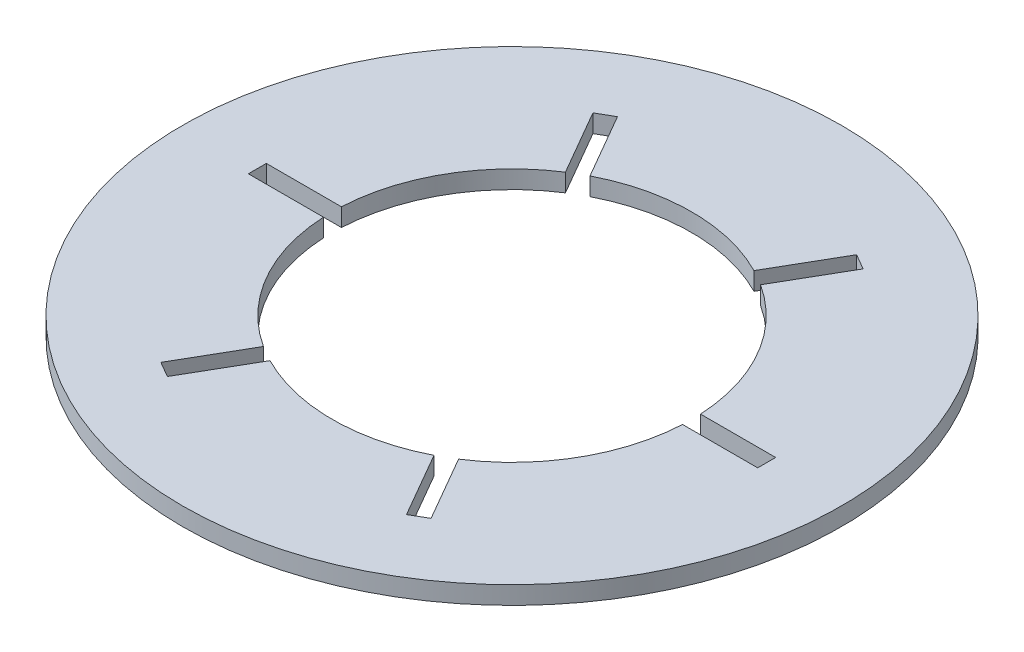
SolidWorks part; units mm, degrees
ref_plane "Front Plane" through (0, 0, 0) normal (0, 0, 1) x (1, 0, 0)
ref_plane "Top Plane" through (0, 0, 0) normal (0, 1, 0) x (1, 0, 0)
ref_plane "Right Plane" through (0, 0, 0) normal (1, 0, 0) x (0, 0, -1)
sketch "Sketch1" plane through (0, 0, 0) normal (0, 1, 0) x (1, 0, 0)
  circle A0 centre (0, 0) radius 55
  dimension "D1" = 110
extrude "Boss-Extrude1" add sketch "Sketch1" along normal blind 3
sketch "Sketch2" plane through (0, 3, 0) normal (0, 1, 0) x (1, 0, 0)
  circle A0 centre (0, 0) radius 30
  dimension "D1" = 60
extrude "Cut-Extrude1" cut sketch "Sketch2" against normal blind 3
sketch "Sketch3" plane through (0, 3, 0) normal (0, 1, 0) x (1, 0, 0)
  line L0 (73.8169, 0) -> (-73.8169, 0) construction
  line L1 (0, -87.0918) -> (0, 87.0918) construction
  line L3 (-42.5, 1.5) -> (-17.5, 1.5)
  line L4 (-42.5, 1.5) -> (-42.5, -1.5)
  line L5 (-42.5, -1.5) -> (-17.5, -1.5)
  line L6 (-17.5, 1.5) -> (-17.5, -1.5)
  line L7 (-42.5, 1.5) -> (-17.5, -1.5) construction
  line L8 (-42.5, -1.5) -> (-17.5, 1.5) construction
  circle A0 centre (0, 0) radius 30 construction
  point P0 (-30, 0)
  point P6 (0, 0)
  point P10 (0, 0)
  dimension "D1" = 3
  dimension "D2" = 25
extrude "Cut-Extrude2" cut sketch "Sketch3" against normal blind 3
pattern_circular "CirPattern1" count 6 over 360 about axis through (0, 3, 0) along (0, 1, 0) of "Cut-Extrude2"
